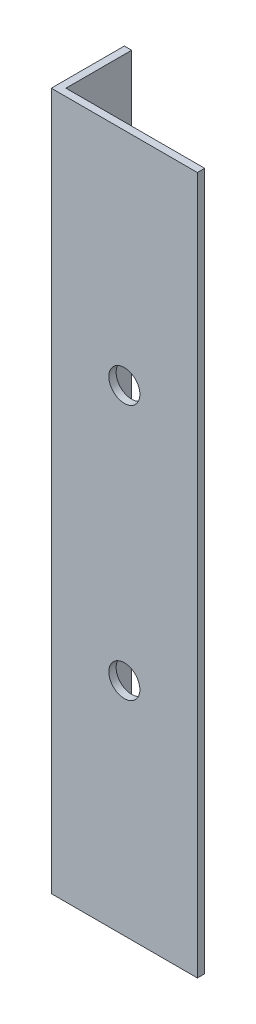
SolidWorks part; units mm, degrees
material "1060 Сплав"
ref_plane "Спереди" through (0, 0, 0) normal (0, 0, 1) x (1, 0, 0)
ref_plane "Сверху" through (0, 0, 0) normal (0, 1, 0) x (1, 0, 0)
ref_plane "Справа" through (0, 0, 0) normal (1, 0, 0) x (0, 0, -1)
sketch "Эскиз1" plane through (0, 0, 0) normal (0, 1, 0) x (1, 0, 0)
  line L0 (0, 0) -> (0, 20)
  line L1 (0, 20) -> (2, 20)
  line L2 (2, 20) -> (2, 2)
  line L3 (2, 2) -> (40, 2)
  line L4 (40, 2) -> (40, 0)
  line L5 (40, 0) -> (0, 0)
  dimension "D1" = 2
  dimension "D2" = 40
  dimension "D3" = 20
extrude "Бобышка-Вытянуть1" add sketch "Эскиз1" along normal blind 191
sketch "Эскиз2" plane through (0, 0, 0) normal (0, 0, 1) x (1, 0, 0)
  line L0 (20, 191) -> (20, 0) construction
  line L1 (0, 191) -> (40, 191) construction
  line L2 (0, 0) -> (40, 0) construction
  line L3 (0, 95.5) -> (40, 95.5) construction
  line L6 (0, 191) -> (0, 0) construction
  line L7 (40, 191) -> (40, 0) construction
  circle A1 centre (20, 130.5) radius 4.25
  circle A3 centre (20, 60.5) radius 4.25
  dimension "D1" = 70
  dimension "D2" = 35
  dimension "D4" = 8.5
extrude "Вырез-Вытянуть1" cut sketch "Эскиз2" against normal through all
